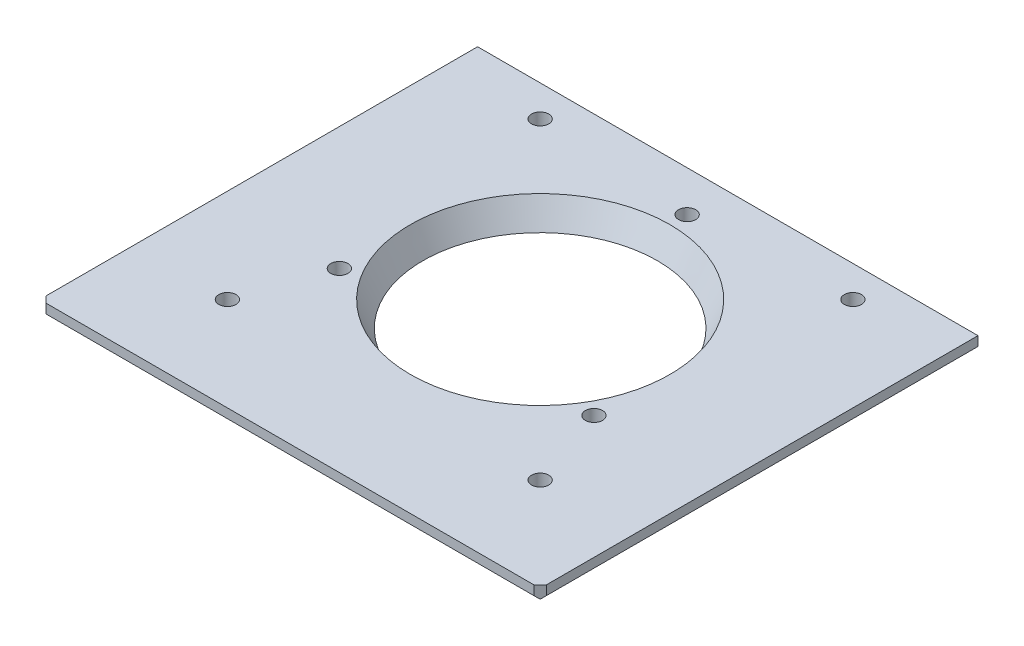
SolidWorks part; units mm, degrees
ref_plane "Front Plane" through (0, 0, 0) normal (0, 0, 1) x (1, 0, 0)
ref_plane "Top Plane" through (0, 0, 0) normal (0, 1, 0) x (1, 0, 0)
ref_plane "Right Plane" through (0, 0, 0) normal (1, 0, 0) x (0, 0, -1)
sketch "Sketch1" plane through (0, 0, 0) normal (0, 1, 0) x (1, 0, 0)
  line L0 (-40, 30) -> (-25, 30)
  line L1 (-40, -30) -> (40, -30)
  line L2 (-40, -30) -> (-40, 30)
  line L3 (-40, 30) -> (40, 30)
  line L4 (40, -30) -> (40, 30)
  line L5 (-40, -30) -> (40, 30) construction
  line L6 (-40, 30) -> (40, -30) construction
  line L7 (-40, -30) -> (40, -30)
  line L8 (-40, -30) -> (-40, -40)
  line L9 (-40, -40) -> (40, -40)
  line L10 (40, -30) -> (40, -40)
  line L11 (-25, 30) -> (-25, 25)
  line L12 (40, 30) -> (25, 30)
  line L13 (25, 30) -> (25, 25)
  line L14 (-25, 25) -> (-25, -25)
  line L15 (25, 25) -> (25, -25)
  circle A0 centre (0, 0) radius 18.75
  arc A1 (0, 23.5) -> (20.3516, -11.75) centre (0, 0) ccw
  circle A5 centre (0, 23.5) radius 1.375
  circle A6 centre (20.3516, -11.75) radius 1.375
  circle A7 centre (-20.3516, -11.75) radius 1.375
  circle A8 centre (-25, 25) radius 1.375
  circle A9 centre (25, 25) radius 1.375
  circle A10 centre (-25, -25) radius 1.375
  circle A11 centre (25, -25) radius 1.375
  point P0 (0, 0)
  point P11 (0, 0)
  dimension "D3" = 10
  dimension "D4" = 37.5
  dimension "D1" = 80
  dimension "D2" = 60
extrude "Boss-Extrude2" add sketch "Sketch1" along normal blind 4 contours L1 L4 L3 L2 A7 A6 A5 A0 | L10 L1 L8 L9 region at (-32.5, 0, -29) region at (0, 0, 35)
chamfer "Chamfer2" distance 2 distance2 4 1 edges at (0, 4, 18.75) first distance on face at (25, 4, 26.375)
extrude "Boss-Extrude3" add sketch "Sketch1<3>" along normal blind 1 contours A7 | A5 | A6
sketch "Sketch1<3>" plane through (0, 0, 0) normal (0, 1, 0) x (1, 0, 0) same geometry as "Sketch1"
chamfer "Chamfer3" distance 0.5 angle 45 4 edges at (-25, 0, 26.375) (25, 0, 26.375) (-25, 0, -23.625) (25, 0, -23.625)
chamfer "Chamfer4" distance 1 angle 45 2 edges at (40, 2, 40) (-40, 2, 40)
chamfer "Chamfer5" distance 2.5 angle 45 3 edges at (40, 0, 4.5) (0, 0, 40) (-40, 0, 4.5)
